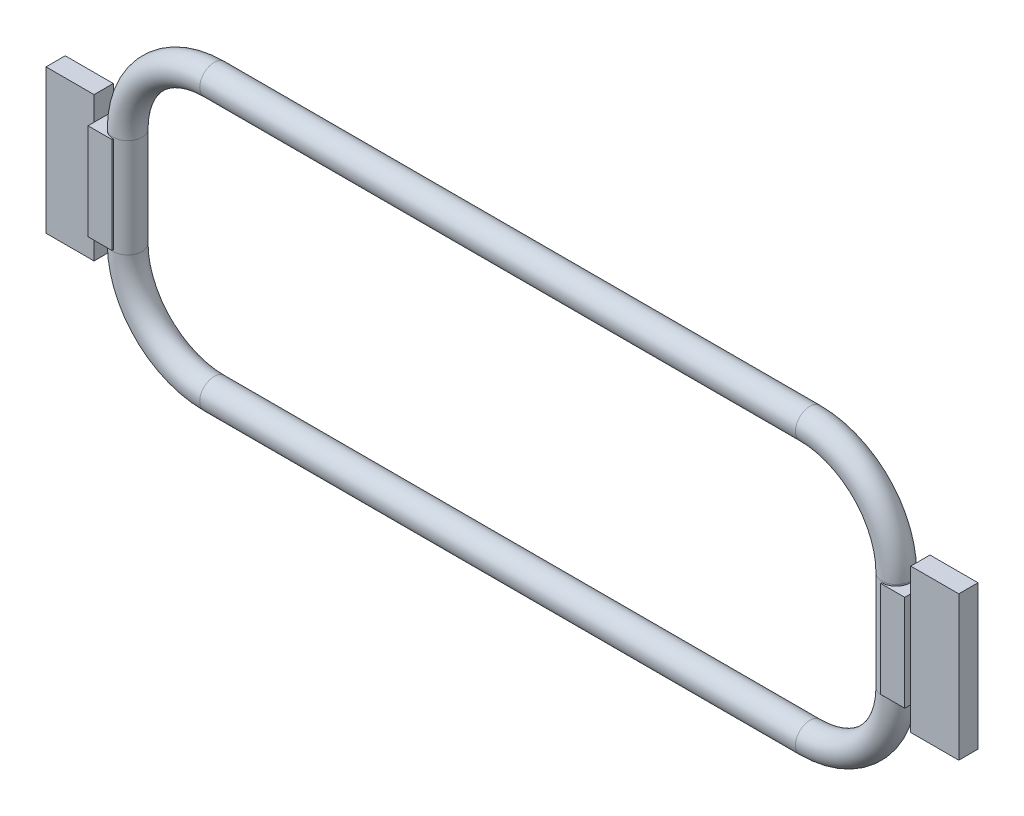
SolidWorks part; units mm, degrees
ref_plane "Front Plane" through (0, 0, 0) normal (0, 0, 1) x (1, 0, 0)
ref_plane "Top Plane" through (0, 0, 0) normal (0, 1, 0) x (1, 0, 0)
ref_plane "Right Plane" through (0, 0, 0) normal (1, 0, 0) x (0, 0, -1)
sketch "Sketch1" plane through (0, 0, 0) normal (0, 0, 1) x (1, 0, 0)
  line L0 (50, 0) -> (-900, 0)
  line L1 (-50, 75) -> (50, 75)
  line L2 (-50, 75) -> (-50, -75)
  line L3 (-50, -75) -> (50, -75)
  line L4 (50, 75) -> (50, -75)
  line L5 (-50, 75) -> (50, -75) construction
  line L6 (-50, -75) -> (50, 75) construction
  line L8 (-800, 75) -> (-900, 75)
  line L9 (-800, 75) -> (-800, -75)
  line L10 (-800, -75) -> (-900, -75)
  line L11 (-900, 75) -> (-900, -75)
  line L12 (-800, 75) -> (-900, -75) construction
  line L13 (-800, -75) -> (-900, 75) construction
  point P0 (0, 0)
  point P8 (-850, 0)
extrude "Boss-Extrude1" add sketch "Sketch1" along normal blind 20 contours L8 L11 L0 L9 | L0 L11 L10 L9 | L4 L3 L2 L1 region at (-850, -37.5, 0) region at (-850, 37.5, 0)
sketch "Sketch4" plane through (0, 0, 0) normal (0, 0, -1) x (-1, 0, 0)
  line L0 (50, -75) -> (-50, -75) construction
  line L1 (50, 75) -> (0, 75)
  line L2 (50, 75) -> (50, -75)
  line L3 (50, -75) -> (0, -75)
  line L4 (0, 75) -> (0, -75)
  line L5 (800, -75) -> (900, -75) construction
  line L6 (800, 75) -> (850, 75)
  line L7 (800, 75) -> (800, -75)
  line L8 (800, -75) -> (850, -75)
  line L9 (850, 75) -> (850, -75)
extrude "Boss-Extrude3" add sketch "Sketch4" along normal blind 6.25
sketch "Sketch5" plane through (0, 0, 20) normal (0, 0, 1) x (1, 0, 0)
  line L0 (-800, -75) -> (-900, -75) construction
  line L1 (-800, 75) -> (-850, 75)
  line L2 (-800, 75) -> (-800, -75)
  line L3 (-800, -75) -> (-850, -75)
  line L4 (-850, 75) -> (-850, -75)
  line L5 (-50, -75) -> (50, -75) construction
  line L6 (-50, 75) -> (0, 75)
  line L7 (-50, 75) -> (-50, -75)
  line L8 (-50, -75) -> (0, -75)
  line L9 (0, 75) -> (0, -75)
extrude "Boss-Extrude4" add sketch "Sketch5" along normal blind 6.25
sketch "Sketch21" plane through (0, 75, 0) normal (0, 1, 0) x (1, 0, 0)
  line L1 (-850, 6.25) -> (0, 6.25)
  line L2 (-850, 6.25) -> (-850, -26.25)
  line L3 (-850, -26.25) -> (0, -26.25)
  line L4 (0, 6.25) -> (0, -26.25)
extrude "Cut-Extrude2" cut sketch "Sketch21" against normal blind 25
extrude "Cut-Extrude3" cut sketch "Sketch21<2>" along normal blind 25 from surface starting at face at (-850, -75, 10)
sketch "Sketch21<2>" plane through (0, 75, 0) normal (0, 1, 0) x (1, 0, 0) same geometry as "Sketch21"
ref_plane "Plane4" through (0, 0, 10) normal (0, 0, 1) x (1, 0, 0)
sketch "Sketch6" plane through (0, 0, 10) normal (0, 0, 1) x (1, 0, 0)
  line L7 (-425, 124.002) -> (-425, -127.0479) construction
  line L9 (-800, 0) -> (-425, 0) construction
  line L10 (-115, -141.5049) -> (-735, -141.5049)
  line L11 (-25, -51.5049) -> (-25, 51.5049)
  line L12 (-115, 141.5049) -> (-735, 141.5049)
  line L13 (-825, -51.5049) -> (-825, 51.5049)
  line L14 (-25, -141.5049) -> (-825, 141.5049) construction
  line L15 (-25, 141.5049) -> (-825, -141.5049) construction
  line L16 (-800, -50) -> (-800, 50) construction
  arc A0 (-735, -141.5049) -> (-825, -51.5049) centre (-735, -51.5049) cw
  arc A1 (-115, -141.5049) -> (-25, -51.5049) centre (-115, -51.5049) ccw
  arc A2 (-25, 51.5049) -> (-115, 141.5049) centre (-115, 51.5049) ccw
  arc A3 (-735, 141.5049) -> (-825, 51.5049) centre (-735, 51.5049) ccw
  point P0 (-425, 0)
  dimension "D1" = 90
sweep "Sweep1" add path "Sketch6" circular profile diameter 30 parameters "D3"=30
ref_plane "Plane5" through (0, 0, 0) normal (0, 1, 0) x (1, 0, 0)
sketch "Sketch19" plane through (0, 0, 0) normal (0, 1, 0) x (1, 0, 0)
  line L0 (-825, -26.25) -> (-825, -25)
  line L3 (-425, -10) -> (-425, -84.3273) construction
  line L4 (-850, -26.25) -> (-800, -26.25) construction
  line L5 (-825, 6.25) -> (-800, 6.25)
  line L6 (-825, 5) -> (-825, 6.25)
  line L7 (-800, 6.25) -> (-850, 6.25) construction
  line L8 (-800, 6.25) -> (-800, -26.25)
  line L9 (-800, -26.25) -> (-825, -26.25)
  line L10 (-50, -26.25) -> (-25, -26.25)
  line L11 (-50, 6.25) -> (-50, -26.25)
  line L12 (-25, 5) -> (-25, 6.25)
  line L13 (-25, 6.25) -> (-50, 6.25)
  line L14 (-25, -26.25) -> (-25, -25)
  arc A0 (-825, -25) -> (-825, 5) centre (-825, -10) ccw
  arc A1 (-25, -25) -> (-25, 5) centre (-25, -10) cw
extrude "Cut-Extrude1" cut sketch "Sketch19" against normal mid plane 100
